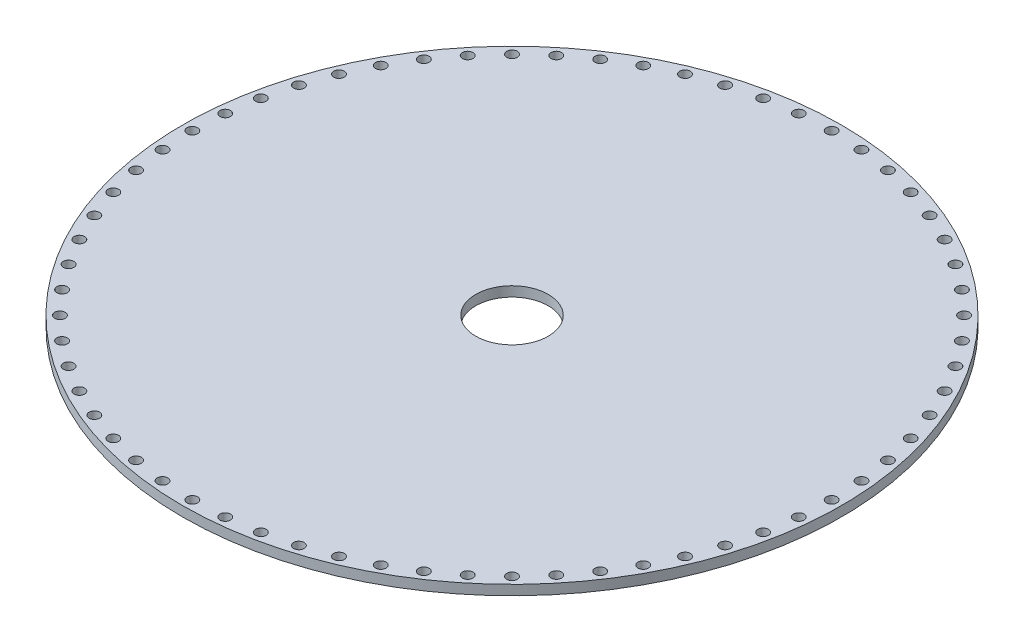
SolidWorks part; units mm, degrees
ref_plane "Front Plane" through (0, 0, 0) normal (0, 0, 1) x (1, 0, 0)
ref_plane "Top Plane" through (0, 0, 0) normal (0, 1, 0) x (1, 0, 0)
ref_plane "Right Plane" through (0, 0, 0) normal (1, 0, 0) x (0, 0, -1)
ref_axis "Axe1" through (0, 55, 0) along (0, -1, 0)
sketch "Esquisse2" plane through (0, 0, 0) normal (0, 0, 1) x (1, 0, 0)
  line L0 (0, 0) -> (100, 0)
  line L1 (100, 0) -> (100, 3)
  line L4 (100, 3) -> (0, 3)
  line L5 (0, 55) -> (0, -55) construction
  line L6 (0, 3) -> (0, 0)
  dimension "D1" = 100
  dimension "D3" = 3
revolve "MainRevolution" add sketch "Esquisse2" angle 360 about axis through (0, 55, 0) along (0, -1, 0)
sketch "Esquisse4" plane through (0, 3, 0) normal (0, 1, 0) x (1, 0, 0)
  circle A0 centre (0, 0) radius 11
  dimension "D1" = 22
extrude "CentralHole" cut sketch "Esquisse4" against normal through all
sketch "Esquisse5" plane through (0, 3, 0) normal (0, 1, 0) x (1, 0, 0)
  circle A0 centre (97, 0) radius 1.6
  point P2 (0, 0)
  dimension "D1" = 3.2
  dimension "D2" = 97
extrude "FixingHole" cut sketch "Esquisse5" against normal through all
pattern_circular "Répétition circulaire1" count 64 every 5.625 about axis through (0, 55, 0) along (0, -1, 0) of "FixingHole"
